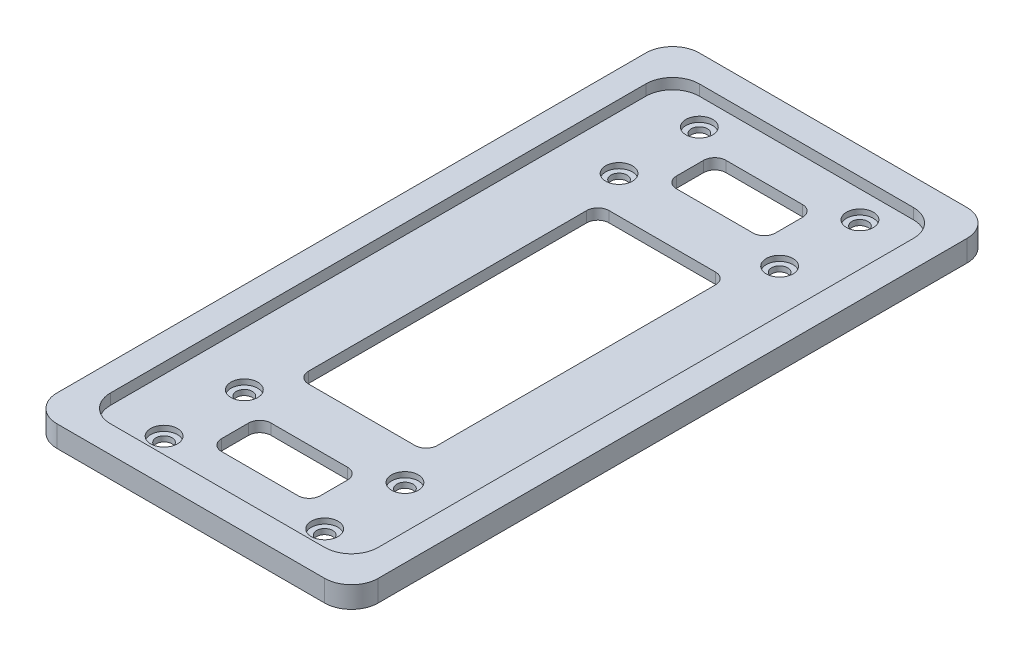
SolidWorks part; units mm, degrees
ref_plane "前视基准面" through (0, 0, 0) normal (0, 0, 1) x (1, 0, 0)
ref_plane "上视基准面" through (0, 0, 0) normal (0, 1, 0) x (1, 0, 0)
ref_plane "右视基准面" through (0, 0, 0) normal (1, 0, 0) x (0, 0, -1)
sketch "草图1" plane through (0, 0, 0) normal (0, 1, 0) x (1, 0, 0)
  line L117 (-199.8401, 146.5986) -> (-199.8401, 7.3826) construction
  line L118 (-199.8401, 131.1197) -> (-224.8401, 131.1197)
  line L119 (-199.8401, 131.1197) -> (-174.8401, 131.1197)
  line L120 (-229.8401, 126.1197) -> (-229.8401, 16.1197)
  line L122 (-199.8401, 11.1197) -> (-174.8401, 11.1197)
  line L123 (-199.8401, 11.1197) -> (-224.8401, 11.1197)
  line L133 (-219.8401, 126.1197) -> (-179.8401, 126.1197)
  line L134 (-174.8401, 121.1197) -> (-174.8401, 21.1197)
  line L135 (-179.8401, 16.1197) -> (-219.8401, 16.1197)
  line L136 (-224.8401, 21.1197) -> (-224.8401, 121.1197)
  line L137 (-169.8401, 126.1197) -> (-169.8401, 16.1197)
  line L139 (-214.8401, 121.1197) -> (-184.8401, 106.1197) construction
  line L148 (-184.8401, 121.1197) -> (-214.8401, 106.1197) construction
  line L149 (-251.4159, 71.1197) -> (-140.8379, 71.1197) construction
  line L150 (-206.9872, 24.003) -> (-192.693, 24.003)
  line L151 (-209.7827, 43.0523) -> (-189.8974, 43.0523)
  line L152 (-211.869, 45.1386) -> (-211.869, 97.1009)
  line L153 (-209.7827, 99.1872) -> (-189.8974, 99.1872)
  line L154 (-187.8112, 45.1386) -> (-187.8112, 97.1009)
  line L155 (-211.869, 43.0523) -> (-187.8112, 99.1872) construction
  line L156 (-211.869, 99.1872) -> (-187.8112, 43.0523) construction
  line L157 (-206.9872, 109.003) -> (-192.693, 109.003)
  line L158 (-209.0735, 111.0893) -> (-209.0735, 116.1502)
  line L159 (-206.9872, 118.2364) -> (-192.693, 118.2364)
  line L160 (-190.6067, 111.0893) -> (-190.6067, 116.1502)
  line L161 (-209.0735, 109.003) -> (-190.6067, 118.2364) construction
  line L162 (-209.0735, 118.2364) -> (-190.6067, 109.003) construction
  line L163 (-190.6067, 31.1502) -> (-190.6067, 26.0893)
  line L164 (-206.9872, 33.2364) -> (-192.693, 33.2364)
  line L165 (-209.0735, 31.1502) -> (-209.0735, 26.0893)
  circle A0 centre (-214.8401, 121.1197) radius 1.5
  circle A65 centre (-184.8401, 121.1197) radius 1.5
  circle A95 centre (-184.8401, 121.1197) radius 2.5
  circle A96 centre (-214.8401, 121.1197) radius 2.5
  arc A137 (-169.8401, 126.1197) -> (-174.8401, 131.1197) centre (-174.8401, 126.1197) ccw
  arc A138 (-229.8401, 126.1197) -> (-224.8401, 131.1197) centre (-224.8401, 126.1197) cw
  arc A139 (-229.8401, 16.1197) -> (-224.8401, 11.1197) centre (-224.8401, 16.1197) ccw
  arc A140 (-169.8401, 16.1197) -> (-174.8401, 11.1197) centre (-174.8401, 16.1197) cw
  circle A145 centre (-214.8401, 21.1197) radius 2.5
  circle A146 centre (-184.8401, 21.1197) radius 2.5
  circle A150 centre (-184.8401, 21.1197) radius 1.5
  circle A152 centre (-214.8401, 21.1197) radius 1.5
  arc A157 (-219.8401, 16.1197) -> (-224.8401, 21.1197) centre (-219.8401, 21.1197) cw
  arc A158 (-179.8401, 16.1197) -> (-174.8401, 21.1197) centre (-179.8401, 21.1197) ccw
  arc A159 (-174.8401, 121.1197) -> (-179.8401, 126.1197) centre (-179.8401, 121.1197) ccw
  arc A160 (-224.8401, 121.1197) -> (-219.8401, 126.1197) centre (-219.8401, 121.1197) cw
  circle A167 centre (-214.8401, 106.1197) radius 1.5
  circle A168 centre (-214.8401, 106.1197) radius 2.5
  circle A169 centre (-184.8401, 36.1197) radius 1.5
  circle A170 centre (-184.8401, 36.1197) radius 2.5
  circle A171 centre (-214.8401, 36.1197) radius 1.5
  circle A172 centre (-214.8401, 36.1197) radius 2.5
  circle A173 centre (-184.8401, 106.1197) radius 1.5
  circle A174 centre (-184.8401, 106.1197) radius 2.5
  arc A175 (-209.0735, 26.0893) -> (-206.9872, 24.003) centre (-206.9872, 26.0893) ccw
  arc A176 (-190.6067, 26.0893) -> (-192.693, 24.003) centre (-192.693, 26.0893) cw
  arc A177 (-190.6067, 31.1502) -> (-192.693, 33.2364) centre (-192.693, 31.1502) ccw
  arc A178 (-209.0735, 31.1502) -> (-206.9872, 33.2364) centre (-206.9872, 31.1502) cw
  arc A179 (-209.7827, 43.0523) -> (-211.869, 45.1386) centre (-209.7827, 45.1386) cw
  arc A180 (-189.8974, 43.0523) -> (-187.8112, 45.1386) centre (-189.8974, 45.1386) ccw
  arc A181 (-189.8974, 99.1872) -> (-187.8112, 97.1009) centre (-189.8974, 97.1009) cw
  arc A182 (-209.7827, 99.1872) -> (-211.869, 97.1009) centre (-209.7827, 97.1009) ccw
  arc A183 (-209.0735, 111.0893) -> (-206.9872, 109.003) centre (-206.9872, 111.0893) ccw
  arc A184 (-190.6067, 111.0893) -> (-192.693, 109.003) centre (-192.693, 111.0893) cw
  arc A185 (-190.6067, 116.1502) -> (-192.693, 118.2364) centre (-192.693, 116.1502) ccw
  arc A186 (-209.0735, 116.1502) -> (-206.9872, 118.2364) centre (-206.9872, 116.1502) cw
  point P29 (-199.8401, 108.6197)
  point P32 (-189.7296, 71.1197)
  point P37 (-166.8323, -26.0766)
  point P38 (-199.8401, 71.1197)
  point P43 (-199.8401, 113.6197)
  point P47 (-169.8401, 71.1197)
  point P51 (-229.8401, 71.1197)
  point P62 (-209.0735, 24.003)
  point P65 (-209.8401, 71.1197)
  point P66 (-190.6067, 24.003)
  point P69 (-190.6067, 33.2364)
  point P84 (-199.8401, 33.6197)
  point P86 (-209.0735, 33.2364)
  dimension "D4" = 2.0863
  dimension "D5" = 70
  dimension "D6" = 30
  dimension "D7" = 50
  dimension "D9" = 5
  dimension "D10" = 3
  dimension "D2" = 5
  dimension "D1" = 5
  dimension "D3" = 30
  dimension "D8" = 110
extrude "凸台-拉伸1" add sketch "草图1" along normal blind 4 contours A140 L137 A137 L119 L118 A138 L120 A139 L123 L122 L136 A160 L133 A159 L134 A158 L135 A157 region at (-187.3401, 0, -129.7781)
extrude "凸台-拉伸2" add sketch "草图1<40>" along normal blind 2 contours A160 L136 A157 L135 A158 L134 A159 L133 A182 L153 A181 L154 A180 L151 A179 L152 A170 A168 A145 A96 A95 A146 A172 A174 L165 A178 L164 A177 L163 A176 L150 A175 L158 A186 L159 A185 L160 A184 L157 A183 region at (-199.8401, 0, -124.9114)
sketch "草图1<40>" plane through (0, 0, 0) normal (0, 1, 0) x (1, 0, 0) same geometry as "草图1"
extrude "凸台-拉伸3" add sketch "草图1<41>" along normal blind 1 contours A172 A171 | A145 A152 | A146 A150 | A170 A169 | A168 A167 | A96 A0 | A95 A65 | A174 A173 region at (-187.2694, 0, -121.1197) region at (-217.2694, 0, -121.1197) region at (-217.2694, 0, -21.1197) region at (-187.2694, 0, -21.1197) region at (-217.2694, 0, -106.1197) region at (-187.2694, 0, -36.1197) region at (-217.2694, 0, -36.1197) region at (-187.2694, 0, -106.1197)
sketch "草图1<41>" plane through (0, 0, 0) normal (0, 1, 0) x (1, 0, 0) same geometry as "草图1"
